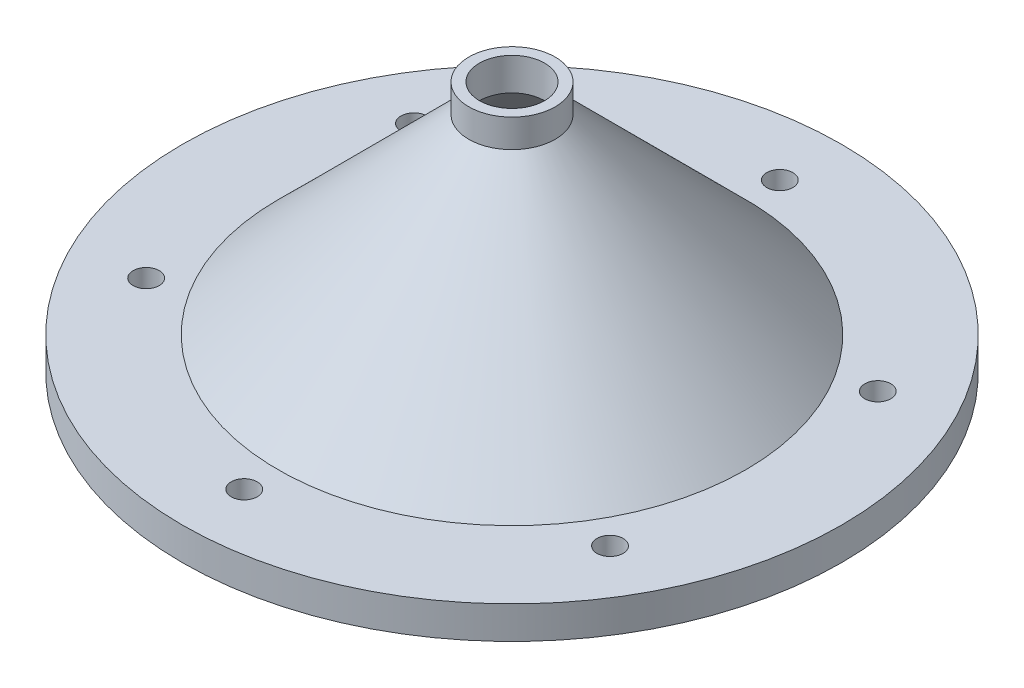
SolidWorks part; units mm, degrees
ref_plane "Front Plane" through (0, 0, 0) normal (0, 0, 1) x (1, 0, 0)
ref_plane "Top Plane" through (0, 0, 0) normal (0, 1, 0) x (1, 0, 0)
ref_plane "Right Plane" through (0, 0, 0) normal (1, 0, 0) x (0, 0, -1)
sketch "Sketch1" plane through (0, 0, 0) normal (0, 1, 0) x (1, 0, 0)
  circle A0 centre (0, 0) radius 76.2
  circle A1 centre (0, 0) radius 72.95
  dimension "D1" = 152.4
  dimension "D2" = 3.25
sketch "Sketch2" plane through (0, 0, 0) normal (0, 0, 1) x (1, 0, 0)
  line L1 (76.2, 0) -> (-76.2, 0) construction
  line L2 (76.2, 0) -> (76.2, 10.3102)
  line L3 (-72.95, 0) -> (-72.95, 3.25) construction
  line L4 (72.95, 0) -> (-72.95, 0) construction
  line L5 (72.95, 0) -> (72.95, 10.3102)
  line L6 (-71.7962, 9) -> (-13.25, 67.5462)
  line L7 (-72.95, 0) -> (-72.95, -1)
  line L8 (-70.95, 5.25) -> (-10, 66.2)
  line L10 (0, 0) -> (0, 106.4824) construction
  line L12 (-10, 70.7962) -> (-5.4038, 70.7962) construction
  line L13 (-10, 70.7962) -> (-10, 66.2)
  line L14 (-10, 70.7962) -> (-10, 76.2)
  line L15 (-13.25, 76.2) -> (-13.25, 63.9447)
  line L16 (-5.4038, 70.7962) -> (0, 70.7962) construction
  line L17 (-5.4038, 70.7962) -> (-0.9519, 75.2481) construction
  line L18 (-10, 70.7962) -> (0, 80.7962) construction
  line L19 (-10, 66.2) -> (-5.4038, 70.7962) construction
  line L20 (-13.25, 67.5462) -> (-10, 70.7962) construction
  line L21 (-13.25, 76.2) -> (-10, 76.2)
  line L22 (-76.2, 0) -> (-72.95, 0)
  line L23 (-72.95, -1) -> (-70.95, -1)
  line L24 (-70.95, -1) -> (-70.95, 5.25)
  line L25 (-72.95, 3.25) -> (-70.95, 5.25) construction
  line L26 (-76.2, 0) -> (-76.2, -1)
  line L27 (-76.2, -1) -> (-101.2, -1)
  line L28 (-101.2, -1) -> (-101.2, 9)
  line L29 (-101.2, 9) -> (-76.2, 9)
  line L31 (-76.2, 9) -> (-71.7962, 9)
  line L32 (-71.7962, 9) -> (-101.2, 9)
  dimension "D2" = 3.25
  dimension "D4" = 3.25
  dimension "D5" = 10
  dimension "D6" = 76.2
  dimension "D7" = 10
  dimension "D8" = 3.25
  dimension "D9" = 0
  dimension "D10" = 3.25
  dimension "D11" = 2
  dimension "D12" = 1
  dimension "D13" = 25
  dimension "D14" = 10
  dimension "D15" = 1
revolve "Revolve1" add sketch "Sketch2" angle 360 about L10 region at (-41.6782, 37.4282, 0)
sketch "Sketch3" plane through (0, -1, 0) normal (0, -1, 0) x (1, 0, 0)
  line L0 (0, 0) -> (0, 76.2)
  line L1 (0, 76.2) -> (0, 101.2)
  circle A0 centre (0, 0) radius 76.2 construction
  circle A1 centre (0, 0) radius 101.2 construction
  circle A2 centre (0, 82.2) radius 4
  circle A3 centre (71.1873, 41.1) radius 4
  circle A4 centre (71.1873, -41.1) radius 4
  circle A5 centre (0, -82.2) radius 4
  circle A6 centre (-71.1873, -41.1) radius 4
  circle A7 centre (-71.1873, 41.1) radius 4
  point P23 (0, 0)
  dimension "D2" = 8
  dimension "D1" = 6
  dimension "D3" = 6
extrude "Cut-Extrude1" cut sketch "Sketch3" against normal blind 10 contours A7 | A6 | A4 | A3 | L1 A2 | L1 A2 | A5 region at (-1.6977, -1, 82.2) region at (1.6977, -1, 82.2) region at (71.1873, -1, 41.1) region at (71.1873, -1, -41.1) region at (-71.1873, -1, -41.1) region at (-71.1873, -1, 41.1)
